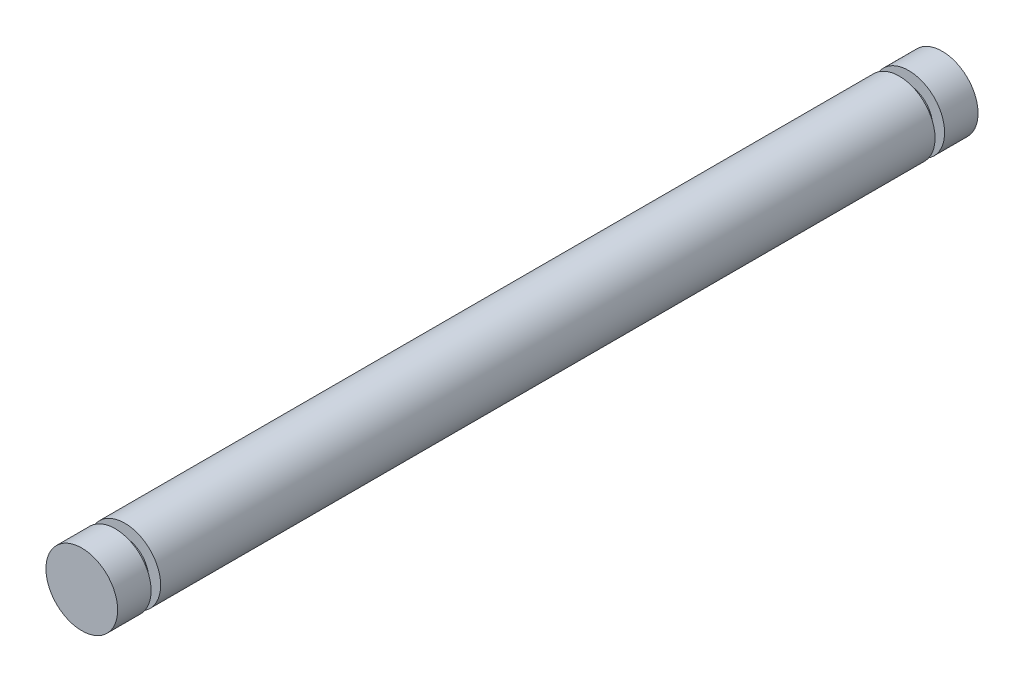
SolidWorks part; units mm, degrees
ref_plane "Front Plane" through (0, 0, 0) normal (0, 0, 1) x (1, 0, 0)
ref_plane "Top Plane" through (0, 0, 0) normal (0, 1, 0) x (1, 0, 0)
ref_plane "Right Plane" through (0, 0, 0) normal (1, 0, 0) x (0, 0, -1)
sketch "Sketch1" plane through (0, 0, 0) normal (0, 0, 1) x (1, 0, 0)
  circle A0 centre (0, 0) radius 4.7625
  dimension "D1" = 9.525
extrude "Boss-Extrude1" add sketch "Sketch1" along normal blind 102.87
sketch "Sketch2" plane through (0, 0, 0) normal (0, 0, -1) x (-1, 0, 0)
  circle A0 centre (0, 0) radius 3.175
  dimension "D1" = 6.35
extrude "Boss-Extrude2" add sketch "Sketch2" along normal blind 1.27
sketch "Sketch3" plane through (0, 0, -1.27) normal (0, 0, -1) x (-1, 0, 0)
  circle A0 centre (0, 0) radius 4.7625
  dimension "D1" = 9.525
extrude "Boss-Extrude3" add sketch "Sketch3" along normal blind 4.445
sketch "Sketch4" plane through (0, 0, 102.87) normal (0, 0, 1) x (1, 0, 0)
  circle A0 centre (0, 0) radius 3.175
  dimension "D1" = 6.35
extrude "Boss-Extrude4" add sketch "Sketch4" along normal blind 1.27
sketch "Sketch5" plane through (0, 0, 104.14) normal (0, 0, 1) x (1, 0, 0)
  circle A0 centre (0, 0) radius 4.7625
  dimension "D1" = 9.525
extrude "Boss-Extrude5" add sketch "Sketch5" along normal blind 4.445
